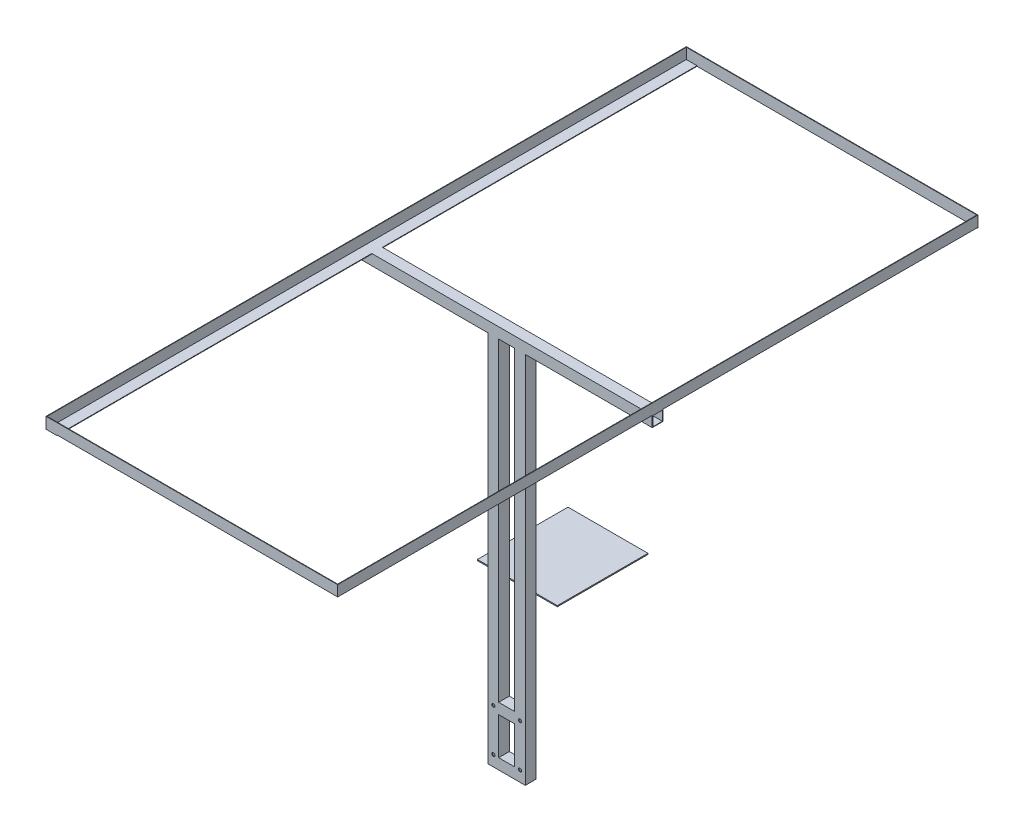
SolidWorks part; units mm, degrees
ref_plane "Front Plane" through (0, 0, 0) normal (0, 0, 1) x (1, 0, 0)
ref_plane "Top Plane" through (0, 0, 0) normal (0, 1, 0) x (1, 0, 0)
ref_plane "Right Plane" through (0, 0, 0) normal (1, 0, 0) x (0, 0, -1)
sketch "Sketch1" plane through (0, 0, 0) normal (0, 1, 0) x (1, 0, 0)
  line L1 (0, 0) -> (20, 0)
  line L2 (0, 0) -> (0, -20)
  line L3 (0, -20) -> (20, -20)
  line L4 (20, 0) -> (20, -20)
  line L5 (-30, 0) -> (-50, 0)
  line L6 (-30, 0) -> (-30, -20)
  line L7 (-30, -20) -> (-50, -20)
  line L8 (-50, 0) -> (-50, -20)
  dimension "D1" = 20
  dimension "D2" = 20
  dimension "D3" = 20
  dimension "D4" = 20
  dimension "D5" = 30
extrude "Extrude-Thin1" add sketch "Sketch1" along normal blind 700 thin thin type one direction reverse wall 1
sketch "Sketch3" plane through (20, 0, 0) normal (1, 0, 0) x (0, 0, -1)
  line L1 (-20, 700) -> (0, 700)
  line L2 (-20, 700) -> (-20, 720)
  line L3 (-20, 720) -> (0, 720)
  line L4 (0, 700) -> (0, 720)
  dimension "D1" = 20
  dimension "D2" = 20
extrude "Extrude-Thin2" add sketch "Sketch3" along normal blind 238 and the other way blind 308 thin thin type one direction reverse wall 1
hole_wizard "Ø6.0mm Dowel Hole1" positions "Sketch4" profile "Sketch5" hole size "Ø6.0" standard "BSI" end condition through all
sketch "Sketch4" plane through (0, 0, 0) normal (0, 0, -1) x (-1, 0, 0)
  line L0 (-20, 0) -> (0, 0) construction
  line L1 (-20, 700) -> (-20, 0) construction
  line L2 (50, 700) -> (50, 0) construction
  line L3 (30, 0) -> (50, 0) construction
  point P0 (40, 20)
  point P2 (-10, 20)
  point P14 (-10, 100)
  point P16 (40, 100)
  dimension "D1" = 20
  dimension "D2" = 10
  dimension "D3" = 10
  dimension "D4" = 20
  dimension "D5" = 10
  dimension "D6" = 10
  dimension "D7" = 80
  dimension "D8" = 80
sketch "Sketch5" plane through (-40, 20, 0) normal (1, 0, 0) x (0, 1, 0)
  line L0 (0, 0) -> (0, 20)
  line L1 (0, 20) -> (3, 20)
  line L2 (3, 20) -> (3, 0)
  line L5 (3, 0) -> (0, 0)
  line L11 (0, -6.35) -> (0, 107.95) construction
  dimension "Thru Hole Dia." = 6
  dimension "Thru Hole Depth" = 20
sketch "Sketch6" plane through (0, 0, 0) normal (0, 0, -1) x (-1, 0, 0)
  line L0 (-238, 720) -> (-258, 720)
  line L1 (288, 720) -> (-258, 720) construction
  line L2 (-258, 720) -> (-258, 740)
  line L3 (268, 720) -> (288, 720)
  line L4 (288, 720) -> (288, 740)
  dimension "D1" = 20
  dimension "D2" = 20
  dimension "D3" = 20
  dimension "D4" = 20
extrude "Extrude-Thin3" add sketch "Sketch6" along normal blind 590 and the other way blind 610 thin thin type one direction wall 1
sketch "Sketch8" plane through (0, 0, -590) normal (0, 0, -1) x (-1, 0, 0)
  line L1 (-258, 740) -> (289, 740)
  line L2 (-258, 740) -> (-258, 719)
  line L3 (-258, 719) -> (289, 719)
  line L4 (289, 740) -> (289, 719)
extrude "Boss-Extrude1" add sketch "Sketch8" along normal blind 1
sketch "Sketch9" plane through (0, 0, 610) normal (0, 0, 1) x (1, 0, 0)
  line L1 (-289, 740) -> (258, 740)
  line L2 (-289, 740) -> (-289, 720)
  line L3 (-289, 720) -> (258, 720)
  line L4 (258, 740) -> (258, 720)
extrude "Boss-Extrude4" add sketch "Sketch9" against normal blind 1
sketch "Sketch10" plane through (-30, 0, 0) normal (1, 0, 0) x (0, 0, -1)
  line L0 (0, 700) -> (0, 0) construction
  line L1 (-20, 0) -> (0, 0)
  line L2 (-20, 0) -> (-20, 20)
  line L3 (-20, 20) -> (0, 20)
  line L4 (0, 0) -> (0, 20)
  line L5 (-20, 700) -> (-20, 0) construction
  line L6 (-20, 110) -> (0, 110)
  line L7 (-20, 110) -> (-20, 90)
  line L8 (-20, 90) -> (0, 90)
  line L9 (0, 110) -> (0, 90)
  dimension "D1" = 20
  dimension "D2" = 20
  dimension "D3" = 70
extrude "Boss-Extrude5" add sketch "Sketch10" along normal blind 30
sketch "Sketch11" plane through (0, 0, 0) normal (0, 0, -1) x (-1, 0, 0)
  line L0 (-20, 0) -> (50, 0) construction
  line L1 (-60, 302) -> (90, 302)
  line L2 (-60, 302) -> (-60, 300)
  line L3 (-60, 300) -> (90, 300)
  line L4 (90, 302) -> (90, 300)
  line L6 (50, 700) -> (50, 0) construction
  dimension "D1" = 2
  dimension "D2" = 300
  dimension "D3" = 150
  dimension "D4" = 40
extrude "Boss-Extrude6" add sketch "Sketch11" along normal blind 170
